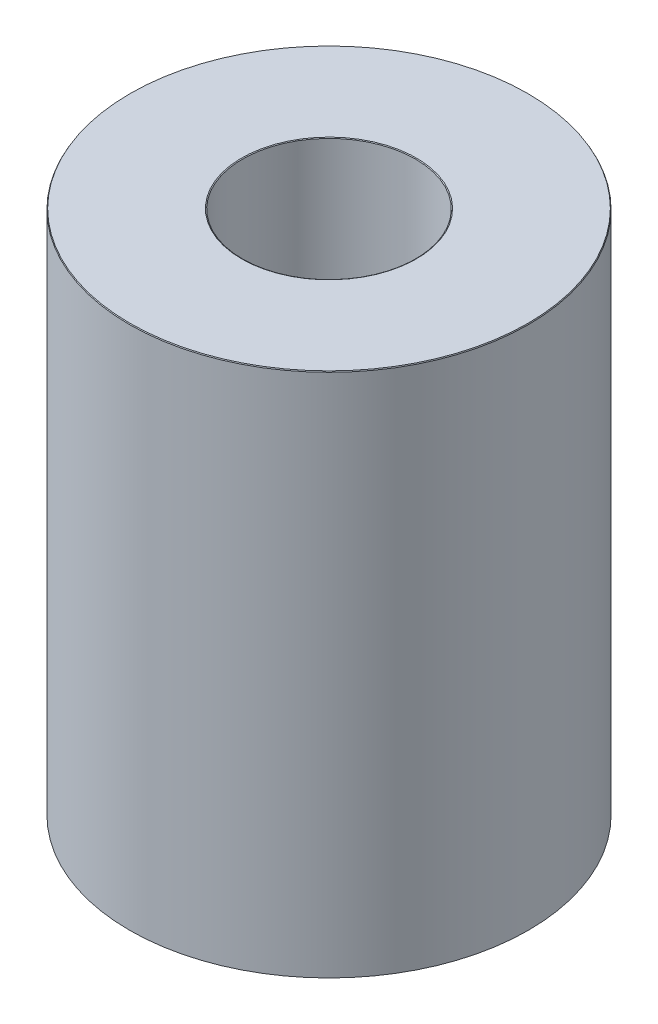
SolidWorks part; units mm, degrees
ref_plane "Front Plane" through (0, 0, 0) normal (0, 0, 1) x (1, 0, 0)
ref_plane "Top Plane" through (0, 0, 0) normal (0, 1, 0) x (1, 0, 0)
ref_plane "Right Plane" through (0, 0, 0) normal (1, 0, 0) x (0, 0, -1)
sketch "Sketch1" plane through (0, 0, 0) normal (0, 1, 0) x (1, 0, 0)
  circle A0 centre (0, 0) radius 52.5
  dimension "SLEEVE_OD" = 105
extrude "Boss-Extrude1" add sketch "Sketch1" along normal blind 138.4238
sketch "Sketch2" plane through (0, 0, 0) normal (0, 1, 0) x (1, 0, 0)
  circle A0 centre (0, 0) radius 22.7721
  dimension "BORE_D" = 45.5442
extrude "Cut-Extrude1" cut sketch "Sketch2" along normal through all
chamfer "Chamfer1" distance 0.2308 angle 30 4 edges at (0, 138.4238, 22.7721) (0, 0, 22.7721) (0, 0, 52.5) (0, 138.4238, 52.5) first distance on face at (0, 138.4238, 22.7721) first distance on face at (0, 0, 22.7721) first distance on face at (0, 138.4238, 52.5)
